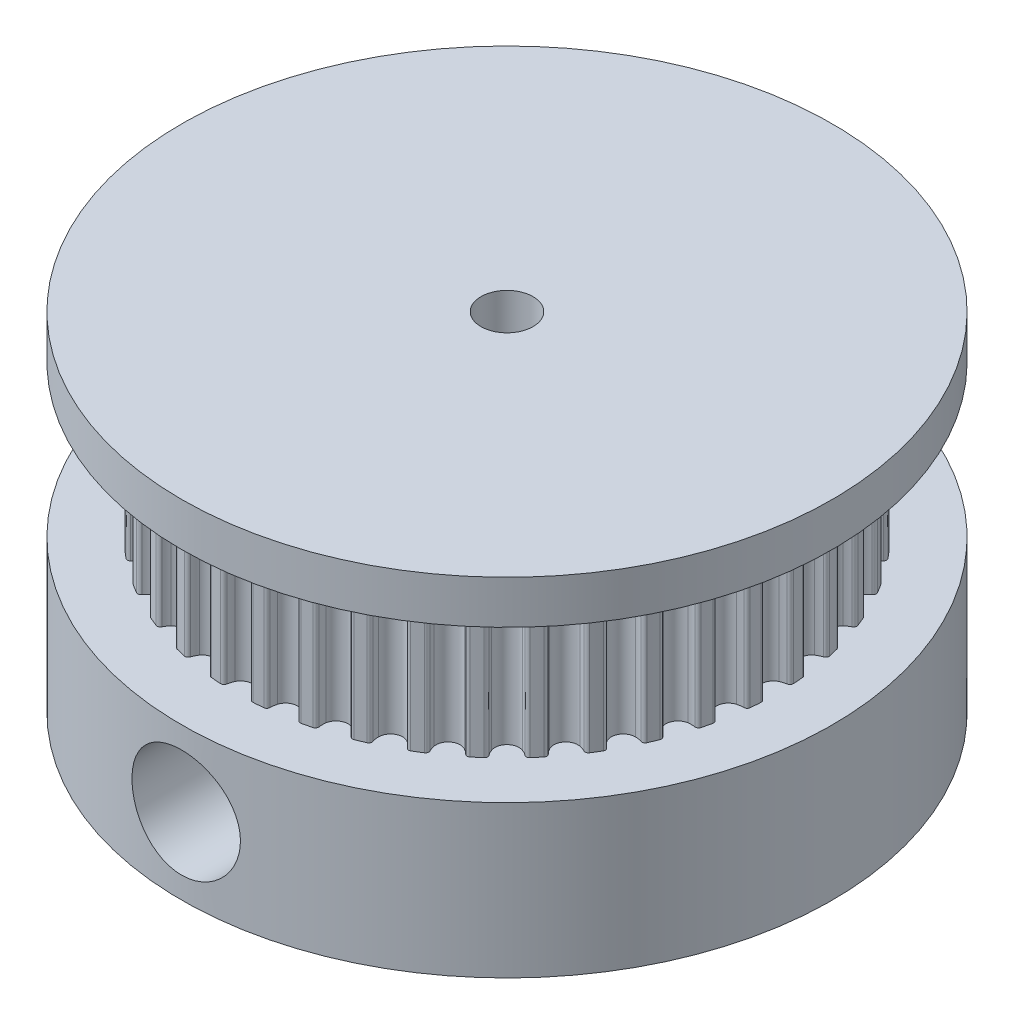
SolidWorks part; units mm, degrees
other "Markup1"
sketch "Sketch11" plane through (-10, 5.5, 10) normal (-0.2341, 0.0958, 0.9675) x (0.972, 0, 0.2351)
sketch "Sketch12" plane through (-9.5, 5.5, 9.5) normal (-0.2341, 0.0958, 0.9675) x (0.972, 0, 0.2351)
sketch "Sketch13" plane through (-9.5, 5.5, 9.5) normal (-0.2341, 0.0958, 0.9675) x (0.972, 0, 0.2351)
ref_plane "Front Plane" through (0, 0, 0) normal (0, 0, 1) x (1, 0, 0)
ref_plane "Top Plane" through (0, 0, 0) normal (0, 1, 0) x (1, 0, 0)
ref_plane "Right Plane" through (0, 0, 0) normal (1, 0, 0) x (0, 0, -1)
sketch "Sketch1" plane through (0, 0, 0) normal (0, 1, 0) x (1, 0, 0)
  line L0 (0, 0) -> (0, 12.7324) construction
  line L2 (0, 0) -> (1.9205, 12.1258) construction
  line L3 (0, 0) -> (2.3939, 12.5053) construction
  line L4 (2.3461, 12.2559) -> (1.2615, 5.4076) construction
  circle A0 centre (0, 0) radius 12.7324
  arc A1 (1.3898, 11.9637) -> (1.8337, 11.5777) centre (1.9205, 12.1258) ccw
  arc A2 (1.3462, 12.2684) -> (1.2108, 12.4195) centre (1.1962, 12.2702) ccw
  arc A3 (1.3462, 12.2684) -> (1.3898, 11.9637) centre (2.3461, 12.2559) ccw
  arc A4 (-1.3898, 11.9637) -> (-1.8337, 11.5777) centre (-1.9205, 12.1258) cw
  arc A5 (1.2108, 12.4195) -> (-1.2108, 12.4195) centre (0, 0) ccw
  arc A6 (-1.3462, 12.2684) -> (-1.3898, 11.9637) centre (-2.3461, 12.2559) cw
  arc A7 (-1.3462, 12.2684) -> (-1.2108, 12.4195) centre (-1.1962, 12.2702) cw
  arc A8 (0.4989, 12.0338) -> (0, 11.722) centre (0, 12.277) cw
  arc A9 (0.5896, 12.3279) -> (0.4989, 12.0338) centre (-0.4, 12.472) cw
  arc A10 (0.5896, 12.3279) -> (0.747, 12.456) centre (0.738, 12.3063) cw
  arc A11 (3.1387, 12.0772) -> (0.747, 12.456) centre (0, 0) ccw
  arc A12 (3.2488, 11.9067) -> (3.1387, 12.0772) centre (3.101, 11.932) ccw
  arc A13 (3.2488, 11.9067) -> (3.2442, 11.599) centre (4.2345, 11.738) ccw
  arc A14 (3.2442, 11.599) -> (3.6223, 11.1483) centre (3.7938, 11.6761) ccw
  arc A15 (2.3752, 11.8076) -> (1.8337, 11.5777) centre (1.9205, 12.1258) cw
  arc A16 (2.5108, 12.0839) -> (2.3752, 11.8076) centre (1.556, 12.381) cw
  arc A17 (2.5108, 12.0839) -> (2.6863, 12.1858) centre (2.654, 12.0393) cw
  arc A18 (4.9893, 11.4375) -> (2.6863, 12.1858) centre (0, 0) ccw
  arc A19 (5.0714, 11.2519) -> (4.9893, 11.4375) centre (4.9294, 11.3) ccw
  arc A20 (5.0714, 11.2519) -> (5.0187, 10.9487) centre (6.0186, 10.931) ccw
  arc A21 (5.0187, 10.9487) -> (5.3217, 10.4444) centre (5.5736, 10.9389) ccw
  arc A22 (4.1931, 11.2906) -> (3.6223, 11.1483) centre (3.7938, 11.6761) cw
  arc A23 (4.3702, 11.5423) -> (4.1931, 11.2906) centre (3.4736, 11.9852) cw
  arc A24 (4.3702, 11.5423) -> (4.5595, 11.6155) centre (4.5047, 11.4759) cw
  arc A25 (6.7171, 10.5162) -> (4.5595, 11.6155) centre (0, 0) ccw
  arc A26 (6.7692, 10.32) -> (6.7171, 10.5162) centre (6.6364, 10.3898) ccw
  arc A27 (6.7692, 10.32) -> (6.6697, 10.0288) centre (7.6545, 9.8549) ccw
  arc A28 (6.6697, 10.0288) -> (6.89, 9.4833) centre (7.2162, 9.9323) ccw
  arc A29 (5.9077, 10.4957) -> (5.3217, 10.4444) centre (5.5736, 10.9389) cw
  arc A30 (6.1221, 10.7166) -> (5.9077, 10.4957) centre (5.3058, 11.2942) cw
  arc A31 (6.1221, 10.7166) -> (6.3205, 10.7593) centre (6.2445, 10.6299) cw
  arc A32 (8.2795, 9.3359) -> (6.3205, 10.7593) centre (0, 0) ccw
  arc A33 (8.3003, 9.134) -> (8.2795, 9.3359) centre (8.18, 9.2237) ccw
  arc A34 (8.3003, 9.134) -> (8.1564, 8.8619) centre (9.1019, 8.5362) ccw
  arc A35 (8.1564, 8.8619) -> (8.2887, 8.2887) centre (8.6811, 8.6811) ccw
  arc A36 (7.4769, 9.4423) -> (6.89, 9.4833) centre (7.2162, 9.9323) cw
  arc A37 (7.7231, 9.6269) -> (7.4769, 9.4423) centre (7.0072, 10.3252) cw
  arc A38 (7.7231, 9.6269) -> (7.9258, 9.6381) centre (7.8305, 9.5222) cw
  arc A39 (9.6381, 7.9258) -> (7.9258, 9.6381) centre (0, 0) ccw
  arc A40 (9.6269, 7.7231) -> (9.6381, 7.9258) centre (9.5222, 7.8305) ccw
  arc A41 (9.6269, 7.7231) -> (9.4423, 7.4769) centre (10.3252, 7.0072) ccw
  arc A42 (9.4423, 7.4769) -> (9.4833, 6.89) centre (9.9323, 7.2162) ccw
  arc A43 (8.8619, 8.1564) -> (8.2887, 8.2887) centre (8.6811, 8.6811) cw
  arc A44 (9.134, 8.3003) -> (8.8619, 8.1564) centre (8.5362, 9.1019) cw
  arc A45 (9.134, 8.3003) -> (9.3359, 8.2795) centre (9.2237, 8.18) cw
  arc A46 (10.7593, 6.3205) -> (9.3359, 8.2795) centre (0, 0) ccw
  arc A47 (10.7166, 6.1221) -> (10.7593, 6.3205) centre (10.6299, 6.2445) ccw
  arc A48 (10.7166, 6.1221) -> (10.4957, 5.9077) centre (11.2942, 5.3058) ccw
  arc A49 (10.4957, 5.9077) -> (10.4444, 5.3217) centre (10.9389, 5.5736) ccw
  arc A50 (10.0288, 6.6697) -> (9.4833, 6.89) centre (9.9323, 7.2162) cw
  arc A51 (10.32, 6.7692) -> (10.0288, 6.6697) centre (9.8549, 7.6545) cw
  arc A52 (10.32, 6.7692) -> (10.5162, 6.7171) centre (10.3898, 6.6364) cw
  arc A53 (11.6155, 4.5595) -> (10.5162, 6.7171) centre (0, 0) ccw
  arc A54 (11.5423, 4.3702) -> (11.6155, 4.5595) centre (11.4759, 4.5047) ccw
  arc A55 (11.5423, 4.3702) -> (11.2906, 4.1931) centre (11.9852, 3.4736) ccw
  arc A56 (11.2906, 4.1931) -> (11.1483, 3.6223) centre (11.6761, 3.7938) ccw
  arc A57 (10.9487, 5.0187) -> (10.4444, 5.3217) centre (10.9389, 5.5736) cw
  arc A58 (11.2519, 5.0714) -> (10.9487, 5.0187) centre (10.931, 6.0186) cw
  arc A59 (11.2519, 5.0714) -> (11.4375, 4.9893) centre (11.3, 4.9294) cw
  arc A60 (12.1858, 2.6863) -> (11.4375, 4.9893) centre (0, 0) ccw
  arc A61 (12.0839, 2.5108) -> (12.1858, 2.6863) centre (12.0393, 2.654) ccw
  arc A62 (12.0839, 2.5108) -> (11.8076, 2.3752) centre (12.381, 1.556) ccw
  arc A63 (11.8076, 2.3752) -> (11.5777, 1.8337) centre (12.1258, 1.9205) ccw
  arc A64 (11.599, 3.2442) -> (11.1483, 3.6223) centre (11.6761, 3.7938) cw
  arc A65 (11.9067, 3.2488) -> (11.599, 3.2442) centre (11.738, 4.2345) cw
  arc A66 (11.9067, 3.2488) -> (12.0772, 3.1387) centre (11.932, 3.101) cw
  arc A67 (12.456, 0.747) -> (12.0772, 3.1387) centre (0, 0) ccw
  arc A68 (12.3279, 0.5896) -> (12.456, 0.747) centre (12.3063, 0.738) ccw
  arc A69 (12.3279, 0.5896) -> (12.0338, 0.4989) centre (12.472, -0.4) ccw
  arc A70 (12.0338, 0.4989) -> (11.722, 0) centre (12.277, 0) ccw
  arc A71 (11.9637, 1.3898) -> (11.5777, 1.8337) centre (12.1258, 1.9205) cw
  arc A72 (12.2684, 1.3462) -> (11.9637, 1.3898) centre (12.2559, 2.3461) cw
  arc A73 (12.2684, 1.3462) -> (12.4195, 1.2108) centre (12.2702, 1.1962) cw
  arc A74 (12.4195, -1.2108) -> (12.4195, 1.2108) centre (0, 0) ccw
  arc A75 (12.2684, -1.3462) -> (12.4195, -1.2108) centre (12.2702, -1.1962) ccw
  arc A76 (12.2684, -1.3462) -> (11.9637, -1.3898) centre (12.2559, -2.3461) ccw
  arc A77 (11.9637, -1.3898) -> (11.5777, -1.8337) centre (12.1258, -1.9205) ccw
  arc A78 (12.0338, -0.4989) -> (11.722, 0) centre (12.277, 0) cw
  arc A79 (12.3279, -0.5896) -> (12.0338, -0.4989) centre (12.472, 0.4) cw
  arc A80 (12.3279, -0.5896) -> (12.456, -0.747) centre (12.3063, -0.738) cw
  arc A81 (12.0772, -3.1387) -> (12.456, -0.747) centre (0, 0) ccw
  arc A82 (11.9067, -3.2488) -> (12.0772, -3.1387) centre (11.932, -3.101) ccw
  arc A83 (11.9067, -3.2488) -> (11.599, -3.2442) centre (11.738, -4.2345) ccw
  arc A84 (11.599, -3.2442) -> (11.1483, -3.6223) centre (11.6761, -3.7938) ccw
  arc A85 (11.8076, -2.3752) -> (11.5777, -1.8337) centre (12.1258, -1.9205) cw
  arc A86 (12.0839, -2.5108) -> (11.8076, -2.3752) centre (12.381, -1.556) cw
  arc A87 (12.0839, -2.5108) -> (12.1858, -2.6863) centre (12.0393, -2.654) cw
  arc A88 (11.4375, -4.9893) -> (12.1858, -2.6863) centre (0, 0) ccw
  arc A89 (11.2519, -5.0714) -> (11.4375, -4.9893) centre (11.3, -4.9294) ccw
  arc A90 (11.2519, -5.0714) -> (10.9487, -5.0187) centre (10.931, -6.0186) ccw
  arc A91 (10.9487, -5.0187) -> (10.4444, -5.3217) centre (10.9389, -5.5736) ccw
  arc A92 (11.2906, -4.1931) -> (11.1483, -3.6223) centre (11.6761, -3.7938) cw
  arc A93 (11.5423, -4.3702) -> (11.2906, -4.1931) centre (11.9852, -3.4736) cw
  arc A94 (11.5423, -4.3702) -> (11.6155, -4.5595) centre (11.4759, -4.5047) cw
  arc A95 (10.5162, -6.7171) -> (11.6155, -4.5595) centre (0, 0) ccw
  arc A96 (10.32, -6.7692) -> (10.5162, -6.7171) centre (10.3898, -6.6364) ccw
  arc A97 (10.32, -6.7692) -> (10.0288, -6.6697) centre (9.8549, -7.6545) ccw
  arc A98 (10.0288, -6.6697) -> (9.4833, -6.89) centre (9.9323, -7.2162) ccw
  arc A99 (10.4957, -5.9077) -> (10.4444, -5.3217) centre (10.9389, -5.5736) cw
  arc A100 (10.7166, -6.1221) -> (10.4957, -5.9077) centre (11.2942, -5.3058) cw
  arc A101 (10.7166, -6.1221) -> (10.7593, -6.3205) centre (10.6299, -6.2445) cw
  arc A102 (9.3359, -8.2795) -> (10.7593, -6.3205) centre (0, 0) ccw
  arc A103 (9.134, -8.3003) -> (9.3359, -8.2795) centre (9.2237, -8.18) ccw
  arc A104 (9.134, -8.3003) -> (8.8619, -8.1564) centre (8.5362, -9.1019) ccw
  arc A105 (8.8619, -8.1564) -> (8.2887, -8.2887) centre (8.6811, -8.6811) ccw
  arc A106 (9.4423, -7.4769) -> (9.4833, -6.89) centre (9.9323, -7.2162) cw
  arc A107 (9.6269, -7.7231) -> (9.4423, -7.4769) centre (10.3252, -7.0072) cw
  arc A108 (9.6269, -7.7231) -> (9.6381, -7.9258) centre (9.5222, -7.8305) cw
  arc A109 (7.9258, -9.6381) -> (9.6381, -7.9258) centre (0, 0) ccw
  arc A110 (7.7231, -9.6269) -> (7.9258, -9.6381) centre (7.8305, -9.5222) ccw
  arc A111 (7.7231, -9.6269) -> (7.4769, -9.4423) centre (7.0072, -10.3252) ccw
  arc A112 (7.4769, -9.4423) -> (6.89, -9.4833) centre (7.2162, -9.9323) ccw
  arc A113 (8.1564, -8.8619) -> (8.2887, -8.2887) centre (8.6811, -8.6811) cw
  arc A114 (8.3003, -9.134) -> (8.1564, -8.8619) centre (9.1019, -8.5362) cw
  arc A115 (8.3003, -9.134) -> (8.2795, -9.3359) centre (8.18, -9.2237) cw
  arc A116 (6.3205, -10.7593) -> (8.2795, -9.3359) centre (0, 0) ccw
  arc A117 (6.1221, -10.7166) -> (6.3205, -10.7593) centre (6.2445, -10.6299) ccw
  arc A118 (6.1221, -10.7166) -> (5.9077, -10.4957) centre (5.3058, -11.2942) ccw
  arc A119 (5.9077, -10.4957) -> (5.3217, -10.4444) centre (5.5736, -10.9389) ccw
  arc A120 (6.6697, -10.0288) -> (6.89, -9.4833) centre (7.2162, -9.9323) cw
  arc A121 (6.7692, -10.32) -> (6.6697, -10.0288) centre (7.6545, -9.8549) cw
  arc A122 (6.7692, -10.32) -> (6.7171, -10.5162) centre (6.6364, -10.3898) cw
  arc A123 (4.5595, -11.6155) -> (6.7171, -10.5162) centre (0, 0) ccw
  arc A124 (4.3702, -11.5423) -> (4.5595, -11.6155) centre (4.5047, -11.4759) ccw
  arc A125 (4.3702, -11.5423) -> (4.1931, -11.2906) centre (3.4736, -11.9852) ccw
  arc A126 (4.1931, -11.2906) -> (3.6223, -11.1483) centre (3.7938, -11.6761) ccw
  arc A127 (5.0187, -10.9487) -> (5.3217, -10.4444) centre (5.5736, -10.9389) cw
  arc A128 (5.0714, -11.2519) -> (5.0187, -10.9487) centre (6.0186, -10.931) cw
  arc A129 (5.0714, -11.2519) -> (4.9893, -11.4375) centre (4.9294, -11.3) cw
  arc A130 (2.6863, -12.1858) -> (4.9893, -11.4375) centre (0, 0) ccw
  arc A131 (2.5108, -12.0839) -> (2.6863, -12.1858) centre (2.654, -12.0393) ccw
  arc A132 (2.5108, -12.0839) -> (2.3752, -11.8076) centre (1.556, -12.381) ccw
  arc A133 (2.3752, -11.8076) -> (1.8337, -11.5777) centre (1.9205, -12.1258) ccw
  arc A134 (3.2442, -11.599) -> (3.6223, -11.1483) centre (3.7938, -11.6761) cw
  arc A135 (3.2488, -11.9067) -> (3.2442, -11.599) centre (4.2345, -11.738) cw
  arc A136 (3.2488, -11.9067) -> (3.1387, -12.0772) centre (3.101, -11.932) cw
  arc A137 (0.747, -12.456) -> (3.1387, -12.0772) centre (0, 0) ccw
  arc A138 (0.5896, -12.3279) -> (0.747, -12.456) centre (0.738, -12.3063) ccw
  arc A139 (0.5896, -12.3279) -> (0.4989, -12.0338) centre (-0.4, -12.472) ccw
  arc A140 (0.4989, -12.0338) -> (0, -11.722) centre (0, -12.277) ccw
  arc A141 (1.3898, -11.9637) -> (1.8337, -11.5777) centre (1.9205, -12.1258) cw
  arc A142 (1.3462, -12.2684) -> (1.3898, -11.9637) centre (2.3461, -12.2559) cw
  arc A143 (1.3462, -12.2684) -> (1.2108, -12.4195) centre (1.1962, -12.2702) cw
  arc A144 (-1.2108, -12.4195) -> (1.2108, -12.4195) centre (0, 0) ccw
  arc A145 (-1.3462, -12.2684) -> (-1.2108, -12.4195) centre (-1.1962, -12.2702) ccw
  arc A146 (-1.3462, -12.2684) -> (-1.3898, -11.9637) centre (-2.3461, -12.2559) ccw
  arc A147 (-1.3898, -11.9637) -> (-1.8337, -11.5777) centre (-1.9205, -12.1258) ccw
  arc A148 (-0.4989, -12.0338) -> (0, -11.722) centre (0, -12.277) cw
  arc A149 (-0.5896, -12.3279) -> (-0.4989, -12.0338) centre (0.4, -12.472) cw
  arc A150 (-0.5896, -12.3279) -> (-0.747, -12.456) centre (-0.738, -12.3063) cw
  arc A151 (-3.1387, -12.0772) -> (-0.747, -12.456) centre (0, 0) ccw
  arc A152 (-3.2488, -11.9067) -> (-3.1387, -12.0772) centre (-3.101, -11.932) ccw
  arc A153 (-3.2488, -11.9067) -> (-3.2442, -11.599) centre (-4.2345, -11.738) ccw
  arc A154 (-3.2442, -11.599) -> (-3.6223, -11.1483) centre (-3.7938, -11.6761) ccw
  arc A155 (-2.3752, -11.8076) -> (-1.8337, -11.5777) centre (-1.9205, -12.1258) cw
  arc A156 (-2.5108, -12.0839) -> (-2.3752, -11.8076) centre (-1.556, -12.381) cw
  arc A157 (-2.5108, -12.0839) -> (-2.6863, -12.1858) centre (-2.654, -12.0393) cw
  arc A158 (-4.9893, -11.4375) -> (-2.6863, -12.1858) centre (0, 0) ccw
  arc A159 (-5.0714, -11.2519) -> (-4.9893, -11.4375) centre (-4.9294, -11.3) ccw
  arc A160 (-5.0714, -11.2519) -> (-5.0187, -10.9487) centre (-6.0186, -10.931) ccw
  arc A161 (-5.0187, -10.9487) -> (-5.3217, -10.4444) centre (-5.5736, -10.9389) ccw
  arc A162 (-4.1931, -11.2906) -> (-3.6223, -11.1483) centre (-3.7938, -11.6761) cw
  arc A163 (-4.3702, -11.5423) -> (-4.1931, -11.2906) centre (-3.4736, -11.9852) cw
  arc A164 (-4.3702, -11.5423) -> (-4.5595, -11.6155) centre (-4.5047, -11.4759) cw
  arc A165 (-6.7171, -10.5162) -> (-4.5595, -11.6155) centre (0, 0) ccw
  arc A166 (-6.7692, -10.32) -> (-6.7171, -10.5162) centre (-6.6364, -10.3898) ccw
  arc A167 (-6.7692, -10.32) -> (-6.6697, -10.0288) centre (-7.6545, -9.8549) ccw
  arc A168 (-6.6697, -10.0288) -> (-6.89, -9.4833) centre (-7.2162, -9.9323) ccw
  arc A169 (-5.9077, -10.4957) -> (-5.3217, -10.4444) centre (-5.5736, -10.9389) cw
  arc A170 (-6.1221, -10.7166) -> (-5.9077, -10.4957) centre (-5.3058, -11.2942) cw
  arc A171 (-6.1221, -10.7166) -> (-6.3205, -10.7593) centre (-6.2445, -10.6299) cw
  arc A172 (-8.2795, -9.3359) -> (-6.3205, -10.7593) centre (0, 0) ccw
  arc A173 (-8.3003, -9.134) -> (-8.2795, -9.3359) centre (-8.18, -9.2237) ccw
  arc A174 (-8.3003, -9.134) -> (-8.1564, -8.8619) centre (-9.1019, -8.5362) ccw
  arc A175 (-8.1564, -8.8619) -> (-8.2887, -8.2887) centre (-8.6811, -8.6811) ccw
  arc A176 (-7.4769, -9.4423) -> (-6.89, -9.4833) centre (-7.2162, -9.9323) cw
  arc A177 (-7.7231, -9.6269) -> (-7.4769, -9.4423) centre (-7.0072, -10.3252) cw
  arc A178 (-7.7231, -9.6269) -> (-7.9258, -9.6381) centre (-7.8305, -9.5222) cw
  arc A179 (-9.6381, -7.9258) -> (-7.9258, -9.6381) centre (0, 0) ccw
  arc A180 (-9.6269, -7.7231) -> (-9.6381, -7.9258) centre (-9.5222, -7.8305) ccw
  arc A181 (-9.6269, -7.7231) -> (-9.4423, -7.4769) centre (-10.3252, -7.0072) ccw
  arc A182 (-9.4423, -7.4769) -> (-9.4833, -6.89) centre (-9.9323, -7.2162) ccw
  arc A183 (-8.8619, -8.1564) -> (-8.2887, -8.2887) centre (-8.6811, -8.6811) cw
  arc A184 (-9.134, -8.3003) -> (-8.8619, -8.1564) centre (-8.5362, -9.1019) cw
  arc A185 (-9.134, -8.3003) -> (-9.3359, -8.2795) centre (-9.2237, -8.18) cw
  arc A186 (-10.7593, -6.3205) -> (-9.3359, -8.2795) centre (0, 0) ccw
  arc A187 (-10.7166, -6.1221) -> (-10.7593, -6.3205) centre (-10.6299, -6.2445) ccw
  arc A188 (-10.7166, -6.1221) -> (-10.4957, -5.9077) centre (-11.2942, -5.3058) ccw
  arc A189 (-10.4957, -5.9077) -> (-10.4444, -5.3217) centre (-10.9389, -5.5736) ccw
  arc A190 (-10.0288, -6.6697) -> (-9.4833, -6.89) centre (-9.9323, -7.2162) cw
  arc A191 (-10.32, -6.7692) -> (-10.0288, -6.6697) centre (-9.8549, -7.6545) cw
  arc A192 (-10.32, -6.7692) -> (-10.5162, -6.7171) centre (-10.3898, -6.6364) cw
  arc A193 (-11.6155, -4.5595) -> (-10.5162, -6.7171) centre (0, 0) ccw
  arc A194 (-11.5423, -4.3702) -> (-11.6155, -4.5595) centre (-11.4759, -4.5047) ccw
  arc A195 (-11.5423, -4.3702) -> (-11.2906, -4.1931) centre (-11.9852, -3.4736) ccw
  arc A196 (-11.2906, -4.1931) -> (-11.1483, -3.6223) centre (-11.6761, -3.7938) ccw
  arc A197 (-10.9487, -5.0187) -> (-10.4444, -5.3217) centre (-10.9389, -5.5736) cw
  arc A198 (-11.2519, -5.0714) -> (-10.9487, -5.0187) centre (-10.931, -6.0186) cw
  arc A199 (-11.2519, -5.0714) -> (-11.4375, -4.9893) centre (-11.3, -4.9294) cw
  arc A200 (-12.1858, -2.6863) -> (-11.4375, -4.9893) centre (0, 0) ccw
  arc A201 (-12.0839, -2.5108) -> (-12.1858, -2.6863) centre (-12.0393, -2.654) ccw
  arc A202 (-12.0839, -2.5108) -> (-11.8076, -2.3752) centre (-12.381, -1.556) ccw
  arc A203 (-11.8076, -2.3752) -> (-11.5777, -1.8337) centre (-12.1258, -1.9205) ccw
  arc A204 (-11.599, -3.2442) -> (-11.1483, -3.6223) centre (-11.6761, -3.7938) cw
  arc A205 (-11.9067, -3.2488) -> (-11.599, -3.2442) centre (-11.738, -4.2345) cw
  arc A206 (-11.9067, -3.2488) -> (-12.0772, -3.1387) centre (-11.932, -3.101) cw
  arc A207 (-12.456, -0.747) -> (-12.0772, -3.1387) centre (0, 0) ccw
  arc A208 (-12.3279, -0.5896) -> (-12.456, -0.747) centre (-12.3063, -0.738) ccw
  arc A209 (-12.3279, -0.5896) -> (-12.0338, -0.4989) centre (-12.472, 0.4) ccw
  arc A210 (-12.0338, -0.4989) -> (-11.722, 0) centre (-12.277, 0) ccw
  arc A211 (-11.9637, -1.3898) -> (-11.5777, -1.8337) centre (-12.1258, -1.9205) cw
  arc A212 (-12.2684, -1.3462) -> (-11.9637, -1.3898) centre (-12.2559, -2.3461) cw
  arc A213 (-12.2684, -1.3462) -> (-12.4195, -1.2108) centre (-12.2702, -1.1962) cw
  arc A214 (-12.4195, 1.2108) -> (-12.4195, -1.2108) centre (0, 0) ccw
  arc A215 (-12.2684, 1.3462) -> (-12.4195, 1.2108) centre (-12.2702, 1.1962) ccw
  arc A216 (-12.2684, 1.3462) -> (-11.9637, 1.3898) centre (-12.2559, 2.3461) ccw
  arc A217 (-11.9637, 1.3898) -> (-11.5777, 1.8337) centre (-12.1258, 1.9205) ccw
  arc A218 (-12.0338, 0.4989) -> (-11.722, 0) centre (-12.277, 0) cw
  arc A219 (-12.3279, 0.5896) -> (-12.0338, 0.4989) centre (-12.472, -0.4) cw
  arc A220 (-12.3279, 0.5896) -> (-12.456, 0.747) centre (-12.3063, 0.738) cw
  arc A221 (-12.0772, 3.1387) -> (-12.456, 0.747) centre (0, 0) ccw
  arc A222 (-11.9067, 3.2488) -> (-12.0772, 3.1387) centre (-11.932, 3.101) ccw
  arc A223 (-11.9067, 3.2488) -> (-11.599, 3.2442) centre (-11.738, 4.2345) ccw
  arc A224 (-11.599, 3.2442) -> (-11.1483, 3.6223) centre (-11.6761, 3.7938) ccw
  arc A225 (-11.8076, 2.3752) -> (-11.5777, 1.8337) centre (-12.1258, 1.9205) cw
  arc A226 (-12.0839, 2.5108) -> (-11.8076, 2.3752) centre (-12.381, 1.556) cw
  arc A227 (-12.0839, 2.5108) -> (-12.1858, 2.6863) centre (-12.0393, 2.654) cw
  arc A228 (-11.4375, 4.9893) -> (-12.1858, 2.6863) centre (0, 0) ccw
  arc A229 (-11.2519, 5.0714) -> (-11.4375, 4.9893) centre (-11.3, 4.9294) ccw
  arc A230 (-11.2519, 5.0714) -> (-10.9487, 5.0187) centre (-10.931, 6.0186) ccw
  arc A231 (-10.9487, 5.0187) -> (-10.4444, 5.3217) centre (-10.9389, 5.5736) ccw
  arc A232 (-11.2906, 4.1931) -> (-11.1483, 3.6223) centre (-11.6761, 3.7938) cw
  arc A233 (-11.5423, 4.3702) -> (-11.2906, 4.1931) centre (-11.9852, 3.4736) cw
  arc A234 (-11.5423, 4.3702) -> (-11.6155, 4.5595) centre (-11.4759, 4.5047) cw
  arc A235 (-10.5162, 6.7171) -> (-11.6155, 4.5595) centre (0, 0) ccw
  arc A236 (-10.32, 6.7692) -> (-10.5162, 6.7171) centre (-10.3898, 6.6364) ccw
  arc A237 (-10.32, 6.7692) -> (-10.0288, 6.6697) centre (-9.8549, 7.6545) ccw
  arc A238 (-10.0288, 6.6697) -> (-9.4833, 6.89) centre (-9.9323, 7.2162) ccw
  arc A239 (-10.4957, 5.9077) -> (-10.4444, 5.3217) centre (-10.9389, 5.5736) cw
  arc A240 (-10.7166, 6.1221) -> (-10.4957, 5.9077) centre (-11.2942, 5.3058) cw
  arc A241 (-10.7166, 6.1221) -> (-10.7593, 6.3205) centre (-10.6299, 6.2445) cw
  arc A242 (-9.3359, 8.2795) -> (-10.7593, 6.3205) centre (0, 0) ccw
  arc A243 (-9.134, 8.3003) -> (-9.3359, 8.2795) centre (-9.2237, 8.18) ccw
  arc A244 (-9.134, 8.3003) -> (-8.8619, 8.1564) centre (-8.5362, 9.1019) ccw
  arc A245 (-8.8619, 8.1564) -> (-8.2887, 8.2887) centre (-8.6811, 8.6811) ccw
  arc A246 (-9.4423, 7.4769) -> (-9.4833, 6.89) centre (-9.9323, 7.2162) cw
  arc A247 (-9.6269, 7.7231) -> (-9.4423, 7.4769) centre (-10.3252, 7.0072) cw
  arc A248 (-9.6269, 7.7231) -> (-9.6381, 7.9258) centre (-9.5222, 7.8305) cw
  arc A249 (-7.9258, 9.6381) -> (-9.6381, 7.9258) centre (0, 0) ccw
  arc A250 (-7.7231, 9.6269) -> (-7.9258, 9.6381) centre (-7.8305, 9.5222) ccw
  arc A251 (-7.7231, 9.6269) -> (-7.4769, 9.4423) centre (-7.0072, 10.3252) ccw
  arc A252 (-7.4769, 9.4423) -> (-6.89, 9.4833) centre (-7.2162, 9.9323) ccw
  arc A253 (-8.1564, 8.8619) -> (-8.2887, 8.2887) centre (-8.6811, 8.6811) cw
  arc A254 (-8.3003, 9.134) -> (-8.1564, 8.8619) centre (-9.1019, 8.5362) cw
  arc A255 (-8.3003, 9.134) -> (-8.2795, 9.3359) centre (-8.18, 9.2237) cw
  arc A256 (-6.3205, 10.7593) -> (-8.2795, 9.3359) centre (0, 0) ccw
  arc A257 (-6.1221, 10.7166) -> (-6.3205, 10.7593) centre (-6.2445, 10.6299) ccw
  arc A258 (-6.1221, 10.7166) -> (-5.9077, 10.4957) centre (-5.3058, 11.2942) ccw
  arc A259 (-5.9077, 10.4957) -> (-5.3217, 10.4444) centre (-5.5736, 10.9389) ccw
  arc A260 (-6.6697, 10.0288) -> (-6.89, 9.4833) centre (-7.2162, 9.9323) cw
  arc A261 (-6.7692, 10.32) -> (-6.6697, 10.0288) centre (-7.6545, 9.8549) cw
  arc A262 (-6.7692, 10.32) -> (-6.7171, 10.5162) centre (-6.6364, 10.3898) cw
  arc A263 (-4.5595, 11.6155) -> (-6.7171, 10.5162) centre (0, 0) ccw
  arc A264 (-4.3702, 11.5423) -> (-4.5595, 11.6155) centre (-4.5047, 11.4759) ccw
  arc A265 (-4.3702, 11.5423) -> (-4.1931, 11.2906) centre (-3.4736, 11.9852) ccw
  arc A266 (-4.1931, 11.2906) -> (-3.6223, 11.1483) centre (-3.7938, 11.6761) ccw
  arc A267 (-5.0187, 10.9487) -> (-5.3217, 10.4444) centre (-5.5736, 10.9389) cw
  arc A268 (-5.0714, 11.2519) -> (-5.0187, 10.9487) centre (-6.0186, 10.931) cw
  arc A269 (-5.0714, 11.2519) -> (-4.9893, 11.4375) centre (-4.9294, 11.3) cw
  arc A270 (-2.6863, 12.1858) -> (-4.9893, 11.4375) centre (0, 0) ccw
  arc A271 (-2.5108, 12.0839) -> (-2.6863, 12.1858) centre (-2.654, 12.0393) ccw
  arc A272 (-2.5108, 12.0839) -> (-2.3752, 11.8076) centre (-1.556, 12.381) ccw
  arc A273 (-2.3752, 11.8076) -> (-1.8337, 11.5777) centre (-1.9205, 12.1258) ccw
  arc A274 (-3.2442, 11.599) -> (-3.6223, 11.1483) centre (-3.7938, 11.6761) cw
  arc A275 (-3.2488, 11.9067) -> (-3.2442, 11.599) centre (-4.2345, 11.738) cw
  arc A276 (-3.2488, 11.9067) -> (-3.1387, 12.0772) centre (-3.101, 11.932) cw
  arc A277 (-0.747, 12.456) -> (-3.1387, 12.0772) centre (0, 0) ccw
  arc A278 (-0.5896, 12.3279) -> (-0.747, 12.456) centre (-0.738, 12.3063) ccw
  arc A279 (-0.5896, 12.3279) -> (-0.4989, 12.0338) centre (0.4, 12.472) ccw
  arc A280 (-0.4989, 12.0338) -> (0, 11.722) centre (0, 12.277) ccw
  point P4 (0, 12.4784)
  point P11 (0, 12.7324)
  point P67 (0, 0)
  dimension "D1" = 25.4648
  dimension "D3" = 1
  dimension "D4" = 0.555
  dimension "D2" = 0.15
  dimension "D5" = 0.4
  dimension "D8" = 0.254
  dimension "D7" = 9
  dimension "D6" = 0.254
  dimension "D9" = 40
extrude "Gear" add sketch "Sketch1" along normal mid plane 7 contours A140 A139 A138 A137 A136 A135 A134 A133 A132 A131 A130 A129 A128 A127 A126 A125 A124 A123 A122 A121 A120 A119 A118 A117 A116 A115 A114 A113 A112 A111 A110 A109 A108 A107 A106 A105 A104 A103 A102 A101 A100 A99 A98 A97 A96 A95 A94 A93 A92 A91 A90 region at (0, 0, 0)
sketch "Sketch2" plane through (0, -3.5, 0) normal (0, -1, 0) x (1, 0, 0)
  line L0 (-11.7249, 0) -> (11.7249, 0) construction
  circle A4 centre (0, 0) radius 15
  circle A5 centre (0, 0) radius 1.2
  point P4 (0, 0)
  dimension "D4" = 30
  dimension "D5" = 2.4
extrude "Base" add sketch "Sketch2" along normal blind 7 contours A4 A5 region at (-14.5757, -3.5, 0)
sketch "Sketch3" plane through (0, 0, 0) normal (0, 0, 1) x (1, 0, 0)
  line L0 (0, 0) -> (0, -7) construction
  line L1 (0, -10.06) -> (2.65, -8.53)
  line L2 (2.65, -8.53) -> (2.65, -5.47)
  line L3 (2.65, -5.47) -> (0, -3.94)
  line L4 (0, -3.94) -> (-2.65, -5.47)
  line L5 (-2.65, -5.47) -> (-2.65, -8.53)
  line L6 (-2.65, -8.53) -> (0, -10.06)
  line L7 (-2.65, -8.53) -> (-2.65, -10.5)
  line L9 (-15, -10.5) -> (15, -10.5) construction
  line L10 (-2.65, -10.5) -> (2.65, -10.5)
  line L11 (2.65, -10.5) -> (2.65, -8.53)
  circle A0 centre (0, -7) radius 2.65 construction
  dimension "D1" = 5.3
  dimension "D2" = 7
extrude "Nut Passthrough" cut sketch "Sketch3" along normal blind 3.5 contours L1 L6 | L5 L6 L1 L2 L3 L4 region at (0, -7, 0) region at (1.3533, -9.3439, 0)
sketch "Sketch9" plane through (0, 3.5, 0) normal (0, 1, 0) x (1, 0, 0)
  circle A0 centre (0, 0) radius 15
  dimension "D1" = 30
extrude "Top" add sketch "Sketch9" along normal blind 2
extrude "Shaft Hole" cut sketch "Sketch2<4>" against normal through all contours A5 L0 | L0 A5 region at (0, -3.5, 0.5093) region at (0, -3.5, -0.5093)
sketch "Sketch2<4>" plane through (0, -3.5, 0) normal (0, -1, 0) x (1, 0, 0) same geometry as "Sketch2"
sketch "Sketch10" plane through (0, 0, 0) normal (0, 0, 1) x (1, 0, 0)
  circle A0 centre (0, -7) radius 1.4
  circle A1 centre (0, -7) radius 2.5
  dimension "D1" = 2.8
  dimension "D2" = 5
extrude "Screw Hole" cut sketch "Sketch10" along normal through all contours A0 region at (0, -7, 0)
extrude "Screw Counterbore" cut sketch "Sketch10<3>" along normal through all from offset 5
sketch "Sketch10<3>" plane through (0, 0, 0) normal (0, 0, 1) x (1, 0, 0) same geometry as "Sketch10"
chamfer "Chamfer2" distance 1.1 angle 45 1 edges at (2.5, -7, 5)
sketch "Sketch14" plane through (0, 0, 0) normal (0, 1, 0) x (1, 0, 0)
  circle A0 centre (0, 0) radius 1
  dimension "D1" = 2
extrude "Boss-Extrude1" add sketch "Sketch14" against normal up to surface (10.5 mm away) separate body up to face at (0, -10.5, -15)
equation "\"D1@Sketch1\"=\"pd\""
equation "\"teethNum\"= 40"
equation "\"pitch\"= 2mm"
equation "\"pd\"= \"teethNum\" * \"pitch\" / PI"
equation "\"D9@Sketch1\"=\"teethNum\""
equation "\"outerDia\"= 30"
equation "\"D4@Sketch2\"=\"outerDia\""
equation "\"D1@Sketch9\"=\"outerDia\""
